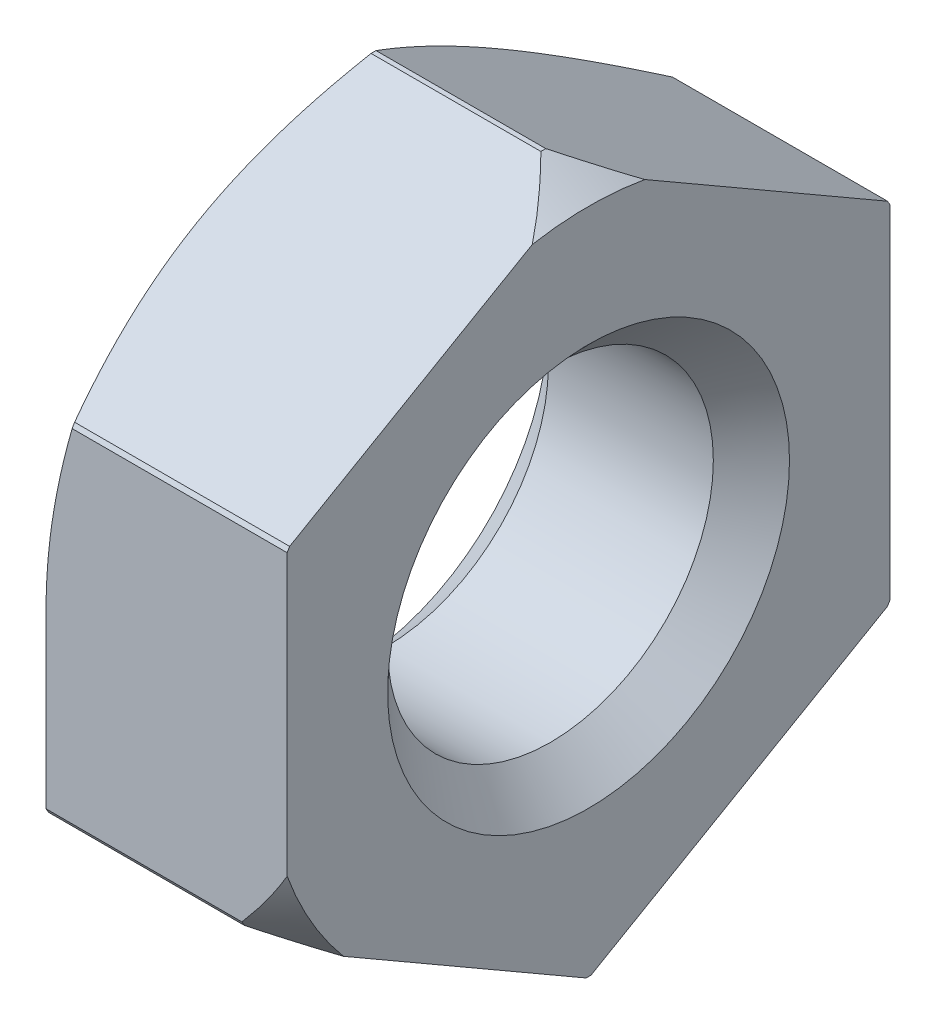
SolidWorks part; units mm, degrees
ref_plane "前基準面" through (0, 0, 0) normal (0, 0, 1) x (1, 0, 0)
ref_plane "上基準面" through (0, 0, 0) normal (0, 1, 0) x (1, 0, 0)
ref_plane "右基準面" through (0, 0, 0) normal (1, 0, 0) x (0, 0, -1)
ref_plane "平面1" through (0, 0, 0) normal (-1, 0, 0) x (0, -1, 0)
sketch "草圖1" plane through (0, 0, 0) normal (-1, 0, 0) x (0, -1, 0)
  line L0 (-1.7462, 2.9754) -> (-3.4499, 0.0246)
  line L1 (-3.4499, -0.0246) -> (-1.7462, -2.9754)
  line L2 (-1.7037, -3) -> (1.7037, -3)
  line L3 (1.7462, -2.9754) -> (3.4499, -0.0246)
  line L4 (3.4499, 0.0246) -> (1.7462, 2.9754)
  line L5 (1.7037, 3) -> (-1.7037, 3)
  arc A0 (-3.4499, 0.0246) -> (-3.4499, -0.0246) centre (0, 0) ccw
  arc A1 (-1.7462, -2.9754) -> (-1.7037, -3) centre (0, 0) ccw
  arc A2 (1.7037, -3) -> (1.7462, -2.9754) centre (0, 0) ccw
  arc A3 (3.4499, -0.0246) -> (3.4499, 0.0246) centre (0, 0) ccw
  arc A4 (1.7462, 2.9754) -> (1.7037, 3) centre (0, 0) ccw
  arc A5 (-1.7037, 3) -> (-1.7462, 2.9754) centre (0, 0) ccw
extrude "填料-伸長1" add sketch "草圖1" against normal blind 2.4
hole_wizard "M3 餘隙孔1" positions "草圖3" profile "草圖2" hole size "M3" standard "Ansi Metric"
sketch "草圖3" plane through (2.4, 0, 0) normal (1, 0, 0) x (0, 0, -1)
  point P0 (0, 0)
sketch "草圖2" plane through (2.4, 0, 0) normal (0, 1, 0) x (0, 0, -1)
  line L0 (0, 0) -> (0, 2.4)
  line L1 (0, 2.4) -> (1.621, 2.4)
  line L2 (1.621, 2.4) -> (1.621, 0)
  line L5 (1.621, 0) -> (0, 0)
  line L11 (0, -6.35) -> (0, 107.95) construction
  dimension "貫穿孔直徑" = 3.242
  dimension "貫穿孔深度" = 2.4
chamfer "導角1" distance 0.45 angle 30 7 edges at (0, -3.45, 0) (2.4, -1.725, 2.9878) (0, 1.725, 2.9878) (0, 3.45, 0) (2.4, 3.45, 0) (0, 1.725, -2.9878) (0, -1.725, -2.9878) first distance on face at (0, 0, -1.621) first distance on face at (1.2, -1.725, 2.9877) first distance on face at (1.2, 3.45, 0)
chamfer "導角2" [suppressed] distance 0.45 angle 30
chamfer "導角3" distance 0.379 angle 45 2 edges at (0, 0, -1.621) (2.4, 0, -1.621)
